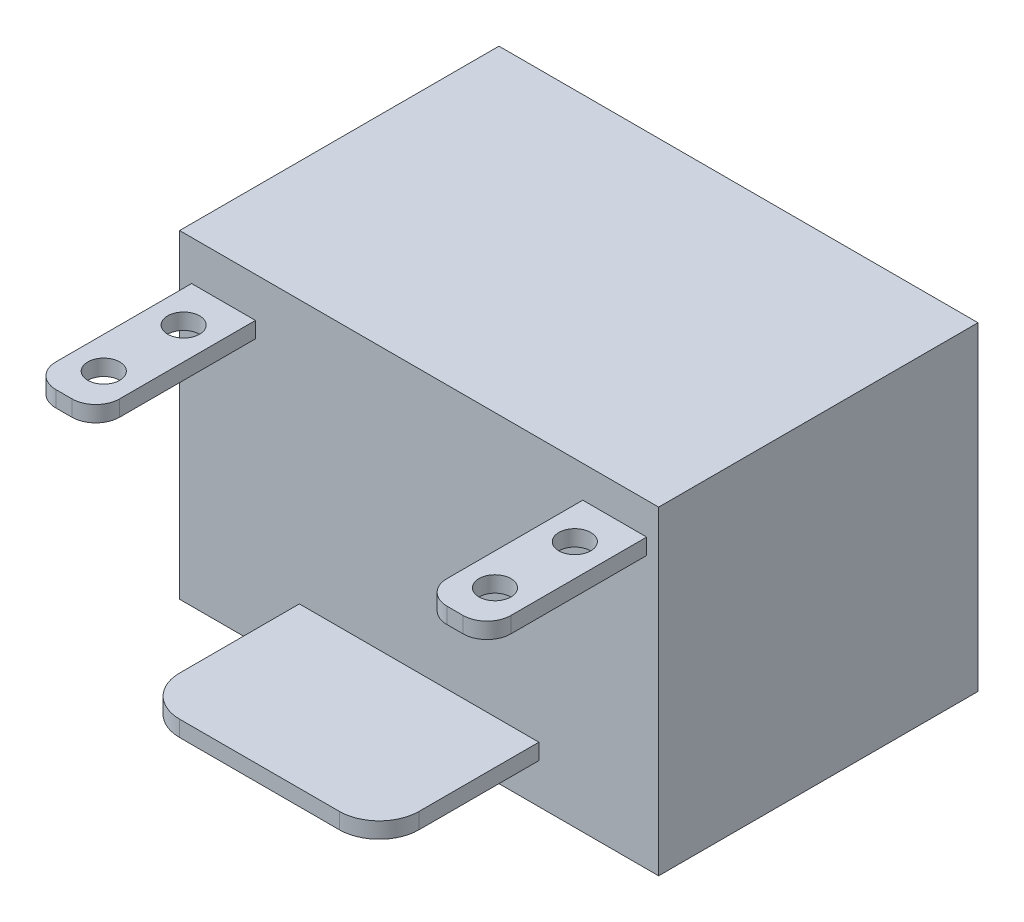
SolidWorks part; units mm, degrees
material "CA"
ref_plane "Ön Düzlem" through (0, 0, 0) normal (0, 0, 1) x (1, 0, 0)
ref_plane "Üst Düzlem" through (0, 0, 0) normal (0, 1, 0) x (1, 0, 0)
ref_plane "Sağ Düzlem" through (0, 0, 0) normal (1, 0, 0) x (0, 0, -1)
sketch "Çizim1" plane through (0, 0, 0) normal (0, 0, 1) x (1, 0, 0)
  line L1 (-30, -20) -> (30, -20)
  line L2 (-30, -20) -> (-30, 20)
  line L3 (-30, 20) -> (30, 20)
  line L4 (30, -20) -> (30, 20)
  line L5 (-30, -20) -> (30, 20) construction
  line L6 (-30, 20) -> (30, -20) construction
  line L7 (-28.5, 13) -> (-20.5, 13)
  line L8 (-28.5, 13) -> (-28.5, 15)
  line L9 (-28.5, 15) -> (-20.5, 15)
  line L10 (-20.5, 13) -> (-20.5, 15)
  line L11 (-28.5, 13) -> (-20.5, 15) construction
  line L12 (-28.5, 15) -> (-20.5, 13) construction
  line L13 (20.5, 14) -> (28.5, 14)
  line L14 (20.5, 14) -> (20.5, 16)
  line L15 (20.5, 16) -> (28.5, 16)
  line L16 (28.5, 14) -> (28.5, 16)
  line L17 (20.5, 14) -> (28.5, 16) construction
  line L18 (20.5, 16) -> (28.5, 14) construction
  line L19 (-15, -15) -> (15, -15)
  line L20 (-15, -15) -> (-15, -13)
  line L21 (-15, -13) -> (15, -13)
  line L22 (15, -15) -> (15, -13)
  line L23 (-15, -15) -> (15, -13) construction
  line L24 (-15, -13) -> (15, -15) construction
  point P0 (0, 0)
  point P6 (-24.5, 14)
  point P11 (24.5, 15)
  point P16 (0, -14)
  dimension "D1" = 60
  dimension "D2" = 40
  dimension "D3" = 8
  dimension "D4" = 2
  dimension "D5" = 8
  dimension "D6" = 2
  dimension "D7" = 41
  dimension "D8" = 20.5
  dimension "D9" = 5
  dimension "D10" = 5
  dimension "D11" = 26
  dimension "D12" = 2
  dimension "D13" = 30
extrude "Yükseklik-Ekstrüzyon1" add sketch "Çizim1" against normal blind 40 contours L1 L4 L3 L2 L22 L19 L20 L21 L16 L13 L14 L15 L10 L7 L8 L9 | L7 L10 L9 L8 | L13 L16 L15 L14 | L19 L22 L21 L20 region at (0, 0.1629, 0) region at (-24.5, 14, 0) region at (24.5, 15, 0) region at (0, -14, 0)
extrude "Yükseklik-Ekstrüzyon2" add sketch "Çizim1<3>" along normal blind 20 contours L7 L10 L9 L8 | L13 L16 L15 L14 | L19 L22 L21 L20 region at (-24.5, 14, 0) region at (24.5, 15, 0) region at (0, -14, 0)
sketch "Çizim1<3>" plane through (0, 0, 0) normal (0, 0, 1) x (1, 0, 0) same geometry as "Çizim1"
ref_plane "Düzlem1" through (0, 16, 0) normal (0, 1, 0) x (1, 0, 0)
sketch "Çizim4" plane through (0, 16, 0) normal (0, 1, 0) x (1, 0, 0)
  line L0 (-30, 0) -> (30, 0) construction
  line L1 (-30, 0) -> (30, 0)
  line L2 (20.5, -20) -> (20.5, 0) construction
  line L3 (-20.5, -20) -> (-20.5, 0) construction
  line L4 (28.5, -20) -> (28.5, 0) construction
  line L5 (20.5, -20) -> (28.5, -20) construction
  line L6 (-28.5, -20) -> (-28.5, 0) construction
  line L7 (-28.5, -20) -> (-20.5, -20) construction
  line L8 (28.5, -17) -> (28.5, 0)
  line L9 (23.5, -20) -> (25.5, -20)
  line L10 (20.5, -17) -> (20.5, 0)
  line L11 (-28.5, -17) -> (-28.5, 0)
  line L12 (-20.5, -17) -> (-20.5, 0)
  line L13 (-25.5, -20) -> (-23.5, -20)
  line L14 (-28.5, -17) -> (-28.5, -20)
  line L15 (-28.5, -20) -> (-20.5, -20)
  line L16 (-20.5, -20) -> (-20.5, -17)
  line L17 (20.5, -17) -> (20.5, -20)
  line L18 (20.5, -20) -> (28.5, -20)
  line L19 (28.5, -20) -> (28.5, -17)
  circle A0 centre (24.5, -5) radius 2
  circle A1 centre (24.5, -15) radius 2
  circle A2 centre (-24.5, -5) radius 2
  circle A3 centre (-24.5, -15) radius 2
  arc A4 (28.5, -17) -> (25.5, -20) centre (25.5, -17) cw
  arc A5 (20.5, -17) -> (23.5, -20) centre (23.5, -17) ccw
  arc A6 (-20.5, -17) -> (-23.5, -20) centre (-23.5, -17) cw
  arc A7 (-25.5, -20) -> (-28.5, -17) centre (-25.5, -17) cw
  dimension "D2" = 4
  dimension "D4" = 4
  dimension "D7" = 4
  dimension "D8" = 4
  dimension "D13" = 3
  dimension "D1" = 5
  dimension "D3" = 4
  dimension "D5" = 15
  dimension "D6" = 4
  dimension "D9" = 5
  dimension "D10" = 4
  dimension "D11" = 4
  dimension "D12" = 15
extrude "Kes-Ekstrüzyon1" cut sketch "Çizim4" against normal through all contours A3 | A2 | A0 | A1 | A5 L17 L18 | L19 A4 L18 | L15 A7 L14 | L16 A6 L15 region at (-27.8299, 16, 19.3299) region at (-21.1701, 16, 19.3299) region at (21.1701, 16, 19.3299) region at (27.8299, 16, 19.3299) region at (24.5, 16, 5) region at (24.5, 16, 15) region at (-24.5, 16, 5) region at (-24.5, 16, 15)
sketch "Çizim5" plane through (0, -15, 0) normal (0, -1, 0) x (1, 0, 0)
  line L0 (-15, 15) -> (-15, 20)
  line L1 (-15, 20) -> (-10, 20)
  line L2 (10, 20) -> (15, 20)
  line L3 (15, 20) -> (15, 15)
  line L4 (-15, 0) -> (15, 0)
  line L5 (15, 0) -> (15, 20)
  line L6 (15, 20) -> (-15, 20)
  line L7 (-15, 20) -> (-15, 0)
  line L8 (-15, 0) -> (15, 0)
  line L9 (15, 0) -> (15, 15)
  line L10 (10, 20) -> (-10, 20)
  line L11 (-15, 15) -> (-15, 0)
  arc A0 (15, 15) -> (10, 20) centre (10, 15) ccw
  arc A1 (-10, 20) -> (-15, 15) centre (-10, 15) ccw
  line M6 (15, 0) -> (15, 20)
  line M7 (15, 20) -> (-15, 20)
  line M8 (-15, 20) -> (-15, 0)
  dimension "D2" = 5
  dimension "D1" = 0
extrude "Kes-Ekstrüzyon2" cut sketch "Çizim5" against normal blind 20 contours A1 M7 M8 | A0 M6 M7 region at (-13.8832, -15, 18.8832) region at (13.8832, -15, 18.8832)
